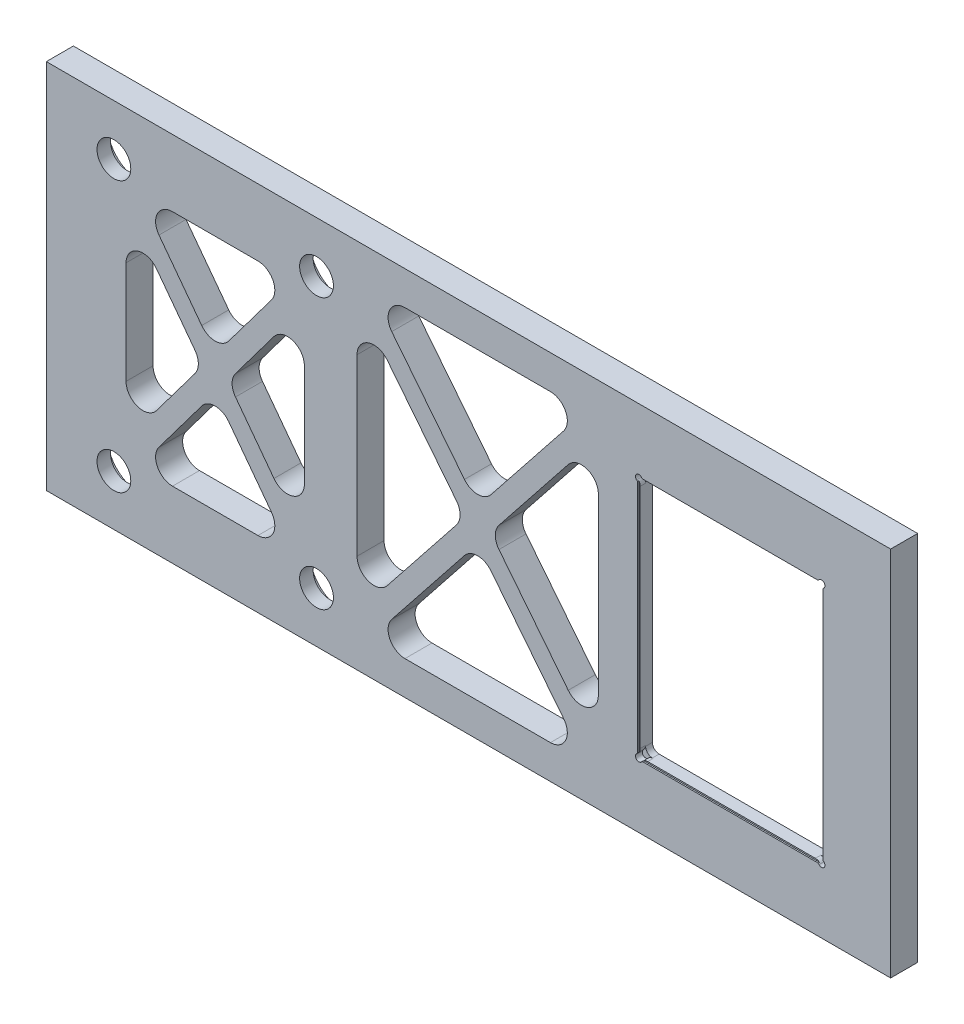
SolidWorks part; units mm, degrees
ref_plane "Front Plane" through (0, 0, 0) normal (0, 0, 1) x (1, 0, 0)
ref_plane "Top Plane" through (0, 0, 0) normal (0, 1, 0) x (1, 0, 0)
ref_plane "Right Plane" through (0, 0, 0) normal (1, 0, 0) x (0, 0, -1)
sketch "Sketch1" plane through (0, 0, 0) normal (0, 0, 1) x (1, 0, 0)
  line L0 (10, 27.5) -> (0, 27.5) construction
  line L1 (0, 0) -> (125, 0)
  line L2 (0, 0) -> (0, 55)
  line L3 (0, 55) -> (125, 55)
  line L4 (125, 0) -> (125, 55)
  line L5 (10, 47.5) -> (40, 47.5) construction
  line L6 (10, 47.5) -> (10, 7.5) construction
  line L7 (10, 7.5) -> (40, 7.5) construction
  line L8 (40, 47.5) -> (40, 7.5) construction
  line L9 (25, 27.5) -> (101.25, 27.5) construction
  line L10 (87.725, 45.425) -> (114.775, 45.425)
  line L11 (87.725, 45.425) -> (87.725, 9.575)
  line L12 (87.725, 9.575) -> (114.775, 9.575)
  line L13 (114.775, 45.425) -> (114.775, 9.575)
  line L14 (10, 47.5) -> (40, 7.5) construction
  line L15 (87.725, 45.425) -> (114.775, 9.575) construction
  circle A0 centre (10, 47.5) radius 2.5
  circle A1 centre (40, 47.5) radius 2.5
  circle A2 centre (10, 7.5) radius 2.5
  circle A3 centre (40, 7.5) radius 2.5
  dimension "D3" = 5
  dimension "D1" = 55
  dimension "D2" = 125
  dimension "D4" = 40
  dimension "D5" = 30
  dimension "D6" = 10
  dimension "D7" = 35.85
  dimension "D8" = 27.05
  dimension "D9" = 76.25
extrude "Boss-Extrude1" add sketch "Sketch1" along normal blind 4
sketch "Sketch2" plane through (0, 0, 4) normal (0, 0, 1) x (1, 0, 0)
  circle A0 centre (87.725, 45.425) radius 0.5
  circle A1 centre (114.775, 45.425) radius 0.5
  circle A2 centre (87.725, 9.575) radius 0.5
  circle A3 centre (114.775, 9.575) radius 0.5
  dimension "D1" = 1
extrude "Cut-Extrude1" cut sketch "Sketch2" against normal blind 1
fillet "Fillet1" radius 1 4 edges at (114.775, 9.575, 1.5) (87.725, 9.575, 1.5) (114.775, 45.425, 1.5) (87.725, 45.425, 1.5)
fillet "Fillet2" radius 1 8 edges at (114.2971, 9.7221, 3.5) (114.6279, 10.0529, 3.5) (87.8721, 10.0529, 3.5) (88.2029, 9.7221, 3.5) (114.6279, 44.9471, 3.5) (114.2971, 45.2779, 3.5) (87.8721, 44.9471, 3.5) (88.2029, 45.2779, 3.5)
sketch "Sketch3" plane through (125, 0, 0) normal (1, 0, 0) x (0, 0, -1)
  line L0 (-3.1, 42.5) -> (-3.1, 12.5) construction
  line L1 (-4, 0) -> (-4, 55) construction
  line L2 (-4, 27.5) -> (-3.1, 27.5) construction
  point P0 (-3.1, 42.5)
  point P1 (-3.1, 12.5)
  point P6 (-3.1, 27.5)
  dimension "D1" = 0.9
  dimension "D2" = 30
hole_wizard "M1.2x0.25 Tapped Hole1" [suppressed] positions "3DSketch2" profile "Sketch6" tap size "M1.2x0.25" standard "IS"
sketch3d "3DSketch2"
  point P0 (125, 42.5, 1.1)
  point P3 (125, 27.5, 1.1)
  point P6 (125, 12.5, 1.1)
sketch "Sketch6" plane through (125, 42.5, 1.1) normal (0, 1, 0) x (0, 0, -1)
  line L0 (0, 0) -> (0, 10.25)
  line L1 (0, 10.25) -> (0.475, 10.25)
  line L2 (0.475, 10.25) -> (0.475, 0)
  line L5 (0.475, 0) -> (0, 0)
  line L11 (0, -6.35) -> (0, 107.95) construction
  dimension "Thru Tap Drill Dia." = 0.95
  dimension "Thru Tap Drill Depth" = 10.25
cosmetic thread "Hole Thread1" [suppressed] parameters "D2"=1.2
cosmetic thread "Hole Thread2" [suppressed] parameters "D2"=1.2
cosmetic thread "Hole Thread3" [suppressed] parameters "D2"=1.2
sketch "Sketch7" plane through (0, 0, 4) normal (0, 0, 1) x (1, 0, 0)
  line L0 (87.525, 27.5) -> (114.975, 27.5) construction
  line L1 (87.525, 45.625) -> (114.975, 45.625)
  line L2 (87.525, 45.625) -> (87.525, 9.375)
  line L3 (87.525, 9.375) -> (114.975, 9.375)
  line L4 (114.975, 45.625) -> (114.975, 9.375)
  line L5 (114.775, 10.693) -> (114.775, 44.307) construction
  line L6 (113.657, 45.425) -> (88.843, 45.425) construction
  line L7 (87.525, 39.9467) -> (87.725, 39.9467) construction
  line L8 (87.725, 44.307) -> (87.725, 10.693) construction
  line L9 (90.6052, 45.425) -> (90.6052, 45.625) construction
  point P8 (114.775, 27.5)
  point P11 (101.25, 45.425)
  point P12 (101.25, 45.625)
  dimension "D1" = 0.2
extrude "Cut-Extrude2" cut sketch "Sketch7" against normal blind 0.2
sketch "Sketch8" plane through (0, 0, 0) normal (0, 0, -1) x (-1, 0, 0)
  line L0 (-116.275, 44.425) -> (-116.275, 10.575)
  line L1 (-113.775, 8.075) -> (-88.725, 8.075)
  line L2 (-86.225, 10.575) -> (-86.225, 44.425)
  line L3 (-88.725, 46.925) -> (-113.775, 46.925)
  line L4 (-114.775, 10.575) -> (-114.775, 44.425) construction
  arc A0 (-116.275, 10.575) -> (-113.775, 8.075) centre (-113.775, 10.575) ccw
  arc A1 (-88.725, 8.075) -> (-86.225, 10.575) centre (-88.725, 10.575) ccw
  arc A2 (-86.225, 44.425) -> (-88.725, 46.925) centre (-88.725, 44.425) ccw
  arc A3 (-113.775, 46.925) -> (-116.275, 44.425) centre (-113.775, 44.425) ccw
  arc A4 (-113.775, 45.425) -> (-114.775, 44.425) centre (-113.775, 44.425) ccw construction
  arc A5 (-87.725, 44.425) -> (-88.725, 45.425) centre (-88.725, 44.425) ccw construction
  arc A6 (-114.775, 10.575) -> (-113.775, 9.575) centre (-113.775, 10.575) ccw construction
  arc A7 (-88.725, 9.575) -> (-87.725, 10.575) centre (-88.725, 10.575) ccw construction
  dimension "D1" = 1.5
extrude "Cut-Extrude3" cut sketch "Sketch8" against normal blind 2
sketch "Sketch9" plane through (0, 0, 0) normal (0, 0, -1) x (-1, 0, 0)
  line L0 (-117.775, 44.425) -> (-117.775, 10.575)
  line L1 (-113.775, 6.575) -> (-88.725, 6.575)
  line L2 (-84.725, 10.575) -> (-84.725, 44.425)
  line L3 (-88.725, 48.425) -> (-113.775, 48.425)
  line L4 (-116.275, 44.425) -> (-116.275, 10.575) construction
  arc A0 (-117.775, 10.575) -> (-113.775, 6.575) centre (-113.775, 10.575) ccw
  arc A1 (-88.725, 6.575) -> (-84.725, 10.575) centre (-88.725, 10.575) ccw
  arc A2 (-84.725, 44.425) -> (-88.725, 48.425) centre (-88.725, 44.425) ccw
  arc A3 (-113.775, 48.425) -> (-117.775, 44.425) centre (-113.775, 44.425) ccw
  arc A4 (-113.775, 46.925) -> (-116.275, 44.425) centre (-113.775, 44.425) ccw construction
  arc A5 (-116.275, 10.575) -> (-113.775, 8.075) centre (-113.775, 10.575) ccw construction
  arc A6 (-88.725, 8.075) -> (-86.225, 10.575) centre (-88.725, 10.575) ccw construction
  arc A7 (-86.225, 44.425) -> (-88.725, 46.925) centre (-88.725, 44.425) ccw construction
  dimension "D1" = 1.5
extrude "Cut-Extrude4" cut sketch "Sketch9" against normal blind 1
sketch "Sketch10" plane through (0, 0, 0) normal (0, 0, -1) x (-1, 0, 0)
  line L0 (0, 55) -> (0, 0) construction
  line L5 (-38.2, 45.1) -> (-11.8, 45.1) construction
  line L6 (-38.2, 45.1) -> (-38.2, 9.9) construction
  line L7 (-38.2, 9.9) -> (-11.8, 9.9) construction
  line L8 (-11.8, 45.1) -> (-11.8, 9.9) construction
  line L9 (-26.875, 27.5) -> (-25, 30) construction
  line L10 (-40, 47.5) -> (-10, 7.5) construction
  line L11 (-40, 47.5) -> (-10, 47.5) construction
  line L12 (-40, 47.5) -> (-40, 7.5) construction
  line L13 (-40, 7.5) -> (-10, 7.5) construction
  line L14 (-10, 47.5) -> (-10, 7.5) construction
  line L15 (-11.8, 45.1) -> (-38.2, 9.9) construction
  line L16 (-38.2, 42.6) -> (-26.875, 27.5)
  line L17 (-26.875, 27.5) -> (-38.2, 12.4)
  line L18 (-38.2, 12.4) -> (-38.2, 42.6)
  line L19 (-36.325, 45.1) -> (-13.675, 45.1)
  line L20 (-13.675, 45.1) -> (-25, 30)
  line L21 (-25, 30) -> (-36.325, 45.1)
  line L22 (-36.325, 9.9) -> (-25, 25)
  line L23 (-25, 25) -> (-13.675, 9.9)
  line L24 (-13.675, 9.9) -> (-36.325, 9.9)
  line L25 (-11.8, 42.6) -> (-23.125, 27.5)
  line L26 (-23.125, 27.5) -> (-11.8, 12.4)
  line L27 (-11.8, 12.4) -> (-11.8, 42.6)
  line L28 (-23.125, 27.5) -> (-25, 30) construction
  point P9 (-11.8, 27.5)
  point P12 (0, 27.5)
  dimension "D1" = 3
  dimension "D2" = 3
extrude "Cut-Extrude5" cut sketch "Sketch10" against normal through all
sketch "Sketch11" plane through (0, 0, 0) normal (0, 0, -1) x (-1, 0, 0)
  line L5 (-81.725, 50) -> (-46, 50) construction
  line L6 (-81.725, 50) -> (-81.725, 5) construction
  line L7 (-81.725, 5) -> (-46, 5) construction
  line L8 (-46, 50) -> (-46, 5) construction
  line L9 (-65.7777, 27.5) -> (-63.8625, 29.9125) construction
  line L10 (-81.725, 50) -> (-46, 5) construction
  line L15 (-46, 50) -> (-81.725, 5) construction
  line L16 (-81.725, 47.5875) -> (-65.7777, 27.5)
  line L17 (-65.7777, 27.5) -> (-81.725, 7.4125)
  line L18 (-81.725, 7.4125) -> (-81.725, 47.5875)
  line L19 (-79.8098, 50) -> (-47.9152, 50)
  line L20 (-47.9152, 50) -> (-63.8625, 29.9125)
  line L21 (-63.8625, 29.9125) -> (-79.8098, 50)
  line L22 (-79.8098, 5) -> (-63.8625, 25.0875)
  line L23 (-63.8625, 25.0875) -> (-47.9152, 5)
  line L24 (-47.9152, 5) -> (-79.8098, 5)
  line L25 (-46, 47.5875) -> (-61.9473, 27.5)
  line L26 (-61.9473, 27.5) -> (-46, 7.4125)
  line L27 (-46, 7.4125) -> (-46, 47.5875)
  line L28 (-61.9473, 27.5) -> (-63.8625, 29.9125) construction
  line L29 (-38.2, 42.6) -> (-38.2, 12.4) construction
  line L30 (-84.725, 10.575) -> (-84.725, 44.425) construction
  circle A0 centre (-40, 7.5) radius 2.5 construction
  point P3 (-38.2, 27.5)
  point P9 (-46, 27.5)
  dimension "D1" = 3
  dimension "D2" = 3
  dimension "D3" = 6
  dimension "D4" = 45
extrude "Cut-Extrude6" cut sketch "Sketch11" against normal through all
fillet "Fillet3" radius 2.5 24 edges at (11.8, 12.4, 2) (23.125, 27.5, 2) (11.8, 42.6, 2) (13.675, 9.9, 2) (36.325, 9.9, 2) (25, 25, 2) (38.2, 12.4, 2) (26.875, 27.5, 2) (13.675, 45.1, 2) (36.325, 45.1, 2) (38.2, 42.6, 2) (25, 30, 2) (79.8098, 5, 2) (47.9152, 5, 2) (46, 7.4125, 2) (46, 47.5875, 2) (61.9473, 27.5, 2) (47.9152, 50, 2) (81.725, 7.4125, 2) (63.8625, 25.0875, 2) (65.7777, 27.5, 2) (81.725, 47.5875, 2) (79.8098, 50, 2) (63.8625, 29.9125, 2)
sketch "Sketch12" plane through (0, 0, 0) normal (0, 0, -1) x (-1, 0, 0)
  circle A0 centre (-40, 47.5) radius 5
  circle A1 centre (-10, 47.5) radius 5
  circle A2 centre (-40, 7.5) radius 5
  circle A3 centre (-10, 7.5) radius 5
  dimension "D1" = 10
extrude "Cut-Extrude7" cut sketch "Sketch12" against normal blind 2
